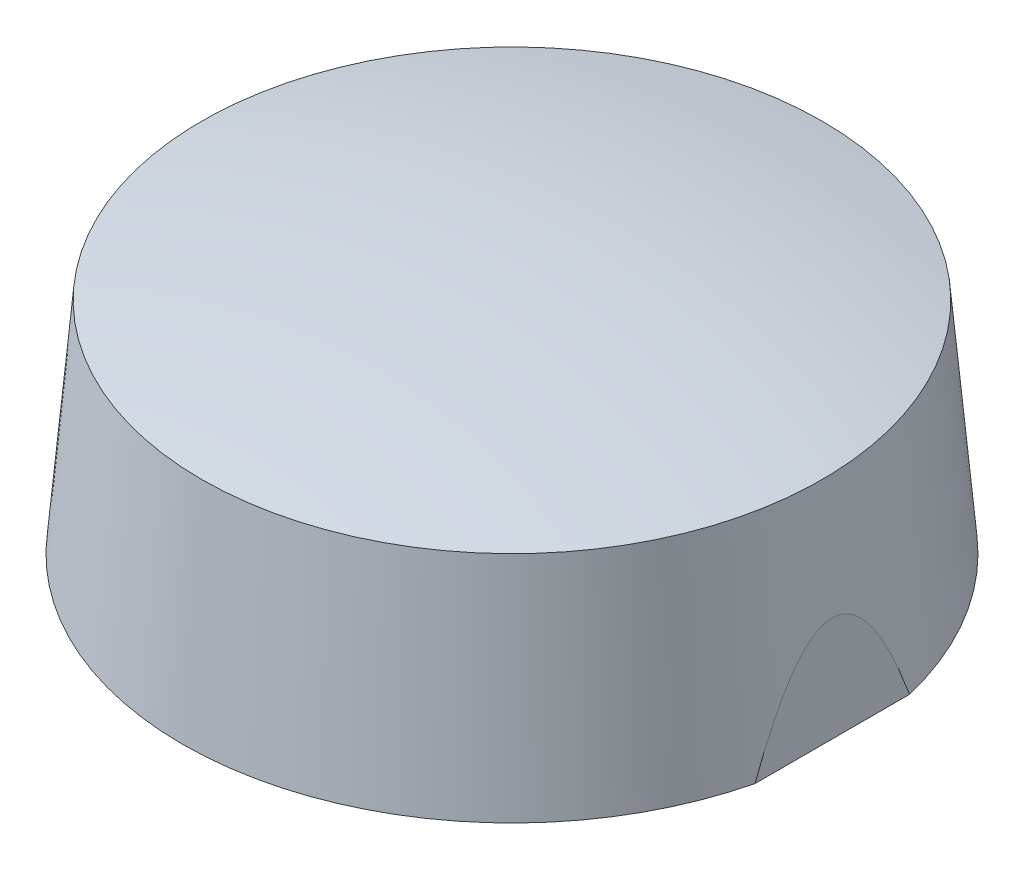
SolidWorks part; units mm, degrees
ref_plane "Front Plane" through (0, 0, 0) normal (0, 0, 1) x (1, 0, 0)
ref_plane "Top Plane" through (0, 0, 0) normal (0, 1, 0) x (1, 0, 0)
ref_plane "Right Plane" through (0, 0, 0) normal (1, 0, 0) x (0, 0, -1)
sketch "Main Body Sketch" plane through (0, 0, 0) normal (0, 1, 0) x (1, 0, 0)
  circle A0 centre (0, 0) radius 48
  dimension "D1" = 96
extrude "Main Body Extrude" add sketch "Main Body Sketch" along normal blind 32 draft 5
sketch "Inner Body Sketch" plane through (0, 0, 0) normal (0, 0, 1) x (1, 0, 0)
  line L0 (-48, 0) -> (48, 0) construction
  line L1 (0, 30) -> (0, 0)
  line L2 (0, 30) -> (44.5, 30)
  line L3 (44.5, 30) -> (44.5, 10)
  line L4 (44.5, 10) -> (46.25, 10)
  line L5 (46.25, 10) -> (46.25, 0)
  line L7 (0, 0) -> (46.25, 0)
  dimension "D1" = 44.5
  dimension "D2" = 46.25
  dimension "D3" = 10
  dimension "D6" = 20
revolve "Inner Body Cut-Revolve" cut sketch "Inner Body Sketch" angle 360 about L1
sketch "Grip Sketch" plane through (0, 0, 0) normal (0, -1, 0) x (1, 0, 0)
  line L0 (-46.663, 11.25) -> (-46.663, -11.25)
  line L1 (-46.663, -11.25) -> (-48, -11.25)
  line L2 (-48, -11.25) -> (-48, 11.25)
  line L3 (-48, 11.25) -> (-46.663, 11.25)
  line L4 (0, 48) -> (0, -48) construction
  line L5 (46.663, -11.25) -> (48, -11.25)
  line L6 (46.663, 11.25) -> (46.663, -11.25)
  line L7 (48, 11.25) -> (46.663, 11.25)
  line L8 (48, -11.25) -> (48, 11.25)
  circle A0 centre (0, 0) radius 48 construction
  dimension "D1" = 22.5
extrude "Grip Extrude" cut sketch "Grip Sketch" against normal up to next
sketch "Thread Base Sketch" plane through (0, 10, 0) normal (0, -1, 0) x (1, 0, 0)
  circle A0 centre (0, 0) radius 44.5
  dimension "D1" = 89
curve "Thread Helix" pitch 5 height 15 radius 44.5 centre (0, 10, 0) axis (0, 1, 0) start towards (0, 0, -1)
sketch "Thread Shape Sketch" plane through (0, 0, 0) normal (1, 0, 0) x (0, 0, -1)
  line L0 (44.5, 27) -> (44.5, 25)
  line L1 (44.5, 25) -> (43.5, 25)
  line L2 (44.5, 27) -> (43.5, 27)
  arc A0 (43.5, 25) -> (43.5, 27) centre (43.5, 26) cw
  dimension "D1" = 1
  dimension "D2" = 2
sweep "Thread Sweep" add profiles "Thread Shape Sketch" path "Thread Helix"
dome "Cap Dome" faces to dome 1 distance 5 reverse direction no elliptical dome no face at (0, 32, 45.2004) parameters "D1"=5
